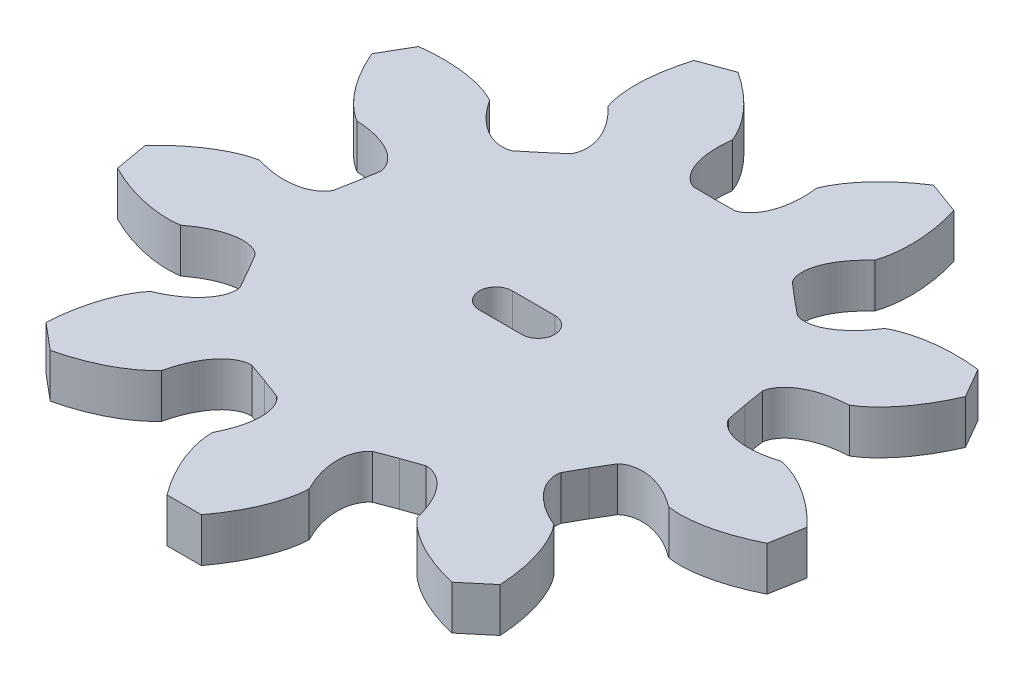
SolidWorks part; units mm, degrees
ref_plane "Plano frontal" through (0, 0, 0) normal (0, 0, 1) x (1, 0, 0)
ref_plane "Plano superior" through (0, 0, 0) normal (0, 1, 0) x (1, 0, 0)
ref_plane "Plano direito" through (0, 0, 0) normal (1, 0, 0) x (0, 0, -1)
sketch "Esboço1" plane through (0, 0, 0) normal (0, 1, 0) x (1, 0, 0)
  line L0 (-25.3837, 16.4538) -> (-26.9413, 13.7561)
  line L1 (-17.2988, 4.9706) -> (-17.6034, 3.104)
  line L2 (-17.6034, 3.104) -> (-17.9556, 1.2457)
  line L3 (-8.8688, 28.9207) -> (-11.796, 27.8553)
  line L4 (-30.0214, -3.712) -> (-29.4805, -6.7798)
  line L5 (-16.4467, -7.3117) -> (-15.4802, -8.9375)
  line L6 (-15.4802, -8.9375) -> (-14.5555, -10.5874)
  line L7 (-10.0566, 14.9272) -> (-11.4898, 13.6931)
  line L8 (-11.4898, 13.6931) -> (-12.9541, 12.4959)
  line L9 (11.796, 27.8553) -> (8.8688, 28.9207)
  line L10 (1.8912, 17.8991) -> (0, 17.875)
  line L11 (0, 17.875) -> (-1.8912, 17.8991)
  line L12 (26.9413, 13.7561) -> (25.3837, 16.4538)
  line L13 (12.9541, 12.4959) -> (11.4898, 13.693)
  line L14 (11.4898, 13.693) -> (10.0566, 14.9272)
  line L15 (29.4805, -6.7798) -> (30.0214, -3.712)
  line L16 (17.9556, 1.2457) -> (17.6034, 3.1039)
  line L17 (17.6034, 3.1039) -> (17.2988, 4.9706)
  line L18 (18.2254, -24.1433) -> (20.6117, -22.1409)
  line L19 (14.5555, -10.5874) -> (15.4802, -8.9375)
  line L20 (15.4802, -8.9375) -> (16.4467, -7.3117)
  line L21 (-1.5575, -30.2099) -> (1.5575, -30.2099)
  line L22 (4.3447, -17.4665) -> (6.1136, -16.797)
  line L23 (6.1136, -16.797) -> (7.899, -16.1728)
  line L24 (-20.6117, -22.1409) -> (-18.2254, -24.1433)
  line L25 (-7.899, -16.1728) -> (-6.1136, -16.797)
  line L26 (-6.1136, -16.797) -> (-4.3447, -17.4665)
  spline S0 degree 3 number of poles 420 (-17.9564, 15.4545) -> (-25.3837, 16.4538)
  spline S1 degree 3 number of poles 364 (-12.9541, 12.4959) -> (-17.9564, 15.4545)
  spline S2 degree 3 number of poles 364 (-22.3622, 7.8235) -> (-17.2988, 4.9706)
  spline S3 degree 3 number of poles 420 (-26.9413, 13.7561) -> (-22.3622, 7.8235)
  spline S4 degree 3 number of poles 364 (-17.9556, 1.2457) -> (-23.6894, 0.2967)
  spline S5 degree 3 number of poles 420 (-23.6894, 0.2967) -> (-30.0214, -3.712)
  spline S6 degree 3 number of poles 420 (-29.4805, -6.7798) -> (-22.1593, -8.381)
  spline S7 degree 3 number of poles 364 (-22.1593, -8.381) -> (-16.4467, -7.3117)
  spline S8 degree 3 number of poles 420 (-3.8215, 23.381) -> (-8.8688, 28.9207)
  spline S9 degree 3 number of poles 364 (-1.8912, 17.8991) -> (-3.8215, 23.381)
  spline S10 degree 3 number of poles 364 (-12.1016, 20.3673) -> (-10.0566, 14.9272)
  spline S11 degree 3 number of poles 420 (-11.796, 27.8553) -> (-12.1016, 20.3673)
  spline S12 degree 3 number of poles 420 (12.1016, 20.3673) -> (11.796, 27.8553)
  spline S13 degree 3 number of poles 364 (10.0566, 14.9272) -> (12.1016, 20.3673)
  spline S14 degree 3 number of poles 364 (3.8215, 23.381) -> (1.8912, 17.8991)
  spline S15 degree 3 number of poles 420 (8.8688, 28.9207) -> (3.8215, 23.381)
  spline S16 degree 3 number of poles 420 (22.3622, 7.8235) -> (26.9413, 13.7561)
  spline S17 degree 3 number of poles 364 (17.2988, 4.9706) -> (22.3622, 7.8235)
  spline S18 degree 3 number of poles 364 (17.9564, 15.4545) -> (12.9541, 12.4959)
  spline S19 degree 3 number of poles 420 (25.3837, 16.4538) -> (17.9564, 15.4545)
  spline S20 degree 3 number of poles 420 (22.1593, -8.381) -> (29.4805, -6.7798)
  spline S21 degree 3 number of poles 364 (16.4467, -7.3117) -> (22.1593, -8.381)
  spline S22 degree 3 number of poles 364 (23.6894, 0.2967) -> (17.9556, 1.2457)
  spline S23 degree 3 number of poles 420 (30.0214, -3.712) -> (23.6894, 0.2967)
  spline S24 degree 3 number of poles 420 (11.5878, -20.6639) -> (18.2254, -24.1433)
  spline S25 degree 3 number of poles 364 (7.899, -16.1728) -> (11.5878, -20.6639)
  spline S26 degree 3 number of poles 364 (18.3378, -15) -> (14.5555, -10.5874)
  spline S27 degree 3 number of poles 420 (20.6117, -22.1409) -> (18.3378, -15)
  spline S28 degree 3 number of poles 420 (-4.4058, -23.278) -> (-1.5575, -30.2099)
  spline S29 degree 3 number of poles 364 (-4.3447, -17.4665) -> (-4.4058, -23.278)
  spline S30 degree 3 number of poles 364 (4.4058, -23.278) -> (4.3447, -17.4665)
  spline S31 degree 3 number of poles 420 (1.5575, -30.2099) -> (4.4058, -23.278)
  spline S32 degree 3 number of poles 420 (-18.3378, -15) -> (-20.6117, -22.1409)
  spline S33 degree 3 number of poles 364 (-14.5555, -10.5874) -> (-18.3378, -15)
  spline S34 degree 3 number of poles 364 (-11.5878, -20.6639) -> (-7.899, -16.1728)
  spline S35 degree 3 number of poles 420 (-18.2254, -24.1433) -> (-11.5878, -20.6639)
  point P76 (0, 0)
  dimension "D1" = 9
extrude "Ressalto-extrusão1" add sketch "Esboço1" along normal blind 4
sketch "Esboço2" plane through (0, 0, 0) normal (0, -1, 0) x (1, 0, 0)
  circle A0 centre (0, 0) radius 1
sketch "Esboço3" plane through (0, 0, 0) normal (0, -1, 0) x (1, 0, 0)
  line L4 (1.9247, -1.5) -> (-1.9247, -1.5)
  line L5 (-1.9247, 1.5) -> (1.9247, 1.5)
  arc A0 (1.9247, -1.5) -> (1.9247, 1.5) centre (1.9247, 0) ccw
  arc A1 (-1.9247, 1.5) -> (-1.9247, -1.5) centre (-1.9247, 0) ccw
  dimension "D1" = 3
  dimension "D2" = 1.5
extrude "Corte-extrusão1" cut sketch "Esboço3" against normal up to next
